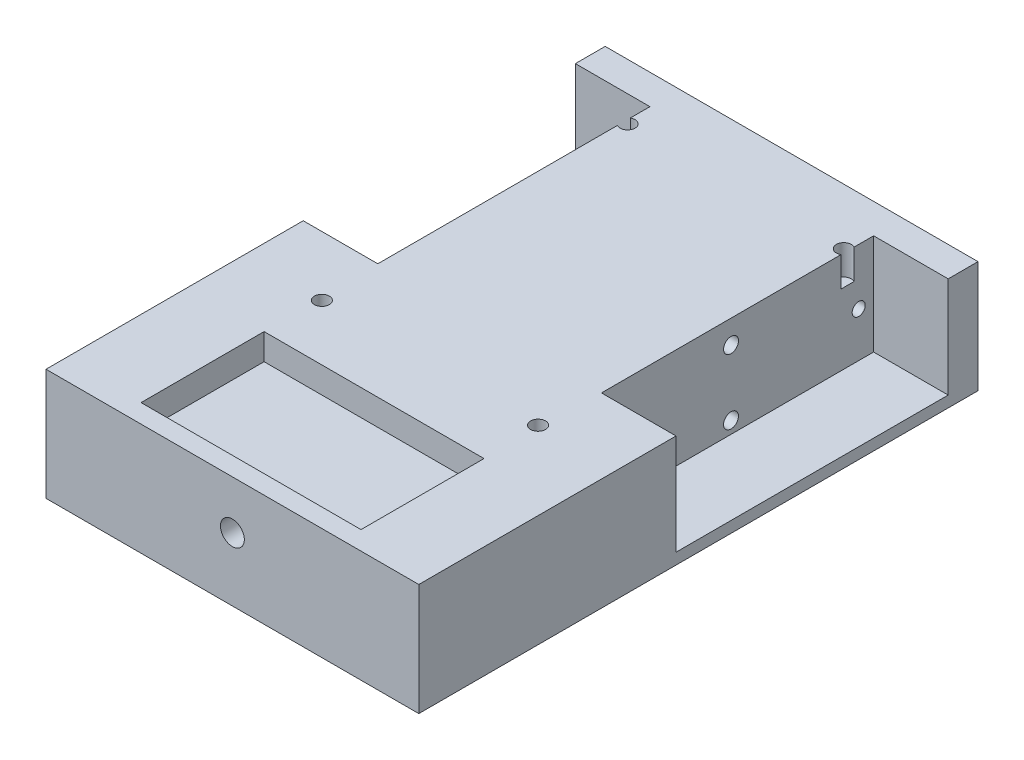
SolidWorks part; units mm, degrees
ref_plane "Front Plane" through (0, 0, 0) normal (0, 0, 1) x (1, 0, 0)
ref_plane "Top Plane" through (0, 0, 0) normal (0, 1, 0) x (1, 0, 0)
ref_plane "Right Plane" through (0, 0, 0) normal (1, 0, 0) x (0, 0, -1)
sketch "Sketch1" plane through (0, 0, 0) normal (0, 1, 0) x (1, 0, 0)
  line L1 (-50, 75) -> (50, 75)
  line L2 (-50, 75) -> (-50, -75)
  line L3 (-50, -75) -> (50, -75)
  line L4 (50, 75) -> (50, -75)
  line L5 (-50, 75) -> (50, -75) construction
  line L6 (-50, -75) -> (50, 75) construction
  point P0 (0, 0)
  dimension "D1" = 100
  dimension "D2" = 150
extrude "box" add sketch "Sketch1" against normal blind 30
sketch "Sketch2" plane through (50, 0, 0) normal (1, 0, 0) x (0, 0, -1)
  line L0 (0, 0) -> (0, -30) construction
  line L1 (-75, -30) -> (75, -30) construction
  line L2 (-75, -15) -> (75, -15) construction
  line L3 (-75, -30) -> (-75, 0) construction
  line L4 (75, -30) -> (75, 0) construction
  line L6 (-6, -3) -> (67, -3)
  line L7 (-6, -3) -> (-6, -27)
  line L8 (-6, -27) -> (67, -27)
  line L9 (67, -3) -> (67, -27)
  line L10 (-6, -3) -> (67, -27) construction
  line L11 (-6, -27) -> (67, -3) construction
  point P11 (30.5, -15)
  dimension "D1" = 24
  dimension "D2" = 73
  dimension "D3" = 8
extrude "motor compartment" cut sketch "Sketch2" against normal blind 20
sketch "Sketch3" plane through (50, 0, 0) normal (1, 0, 0) x (0, 0, -1)
  line L0 (-75, 0) -> (75, 0) construction
  line L1 (-6, -3) -> (4, -3)
  line L2 (-6, -3) -> (-6, 0)
  line L3 (-6, 0) -> (4, 0)
  line L4 (4, -3) -> (4, 0)
  dimension "D1" = 10
extrude "motor wire passthrough" cut sketch "Sketch3" against normal up to surface (20 mm away) up to face at (30, -15, -30.5)
sketch "Sketch4" plane through (30, 0, 0) normal (1, 0, 0) x (0, 0, -1)
  line L0 (67, -15) -> (-49933, -15) construction
  line L1 (67, -27) -> (67, -3) construction
  line L2 (67, -27) -> (67, -3) construction
  line L3 (67, -27) -> (67, -3) construction
  line L4 (28.75, -3) -> (28.75, -27) construction
  line L5 (67, -3) -> (4, -3) construction
  line L6 (-6, -27) -> (67, -27) construction
  circle A0 centre (63, -15) radius 1.75
  circle A1 centre (28.75, -6.25) radius 2
  circle A2 centre (28.75, -23.75) radius 2
  point P4 (67, -15)
  point P19 (0, 0)
  dimension "D1" = 3.5
  dimension "D4" = 4
  dimension "D2" = 4
  dimension "D3" = 34.25
  dimension "D5" = 8.75
extrude "motor screw mount" cut sketch "Sketch4" against normal blind 10
sketch "Sketch9" plane through (50, 0, 0) normal (1, 0, 0) x (0, 0, -1)
  line L1 (4, 0) -> (67, 0)
  line L2 (4, 0) -> (4, -3)
  line L3 (4, -3) -> (67, -3)
  line L4 (67, 0) -> (67, -3)
extrude "remove motor wall" cut sketch "Sketch9" against normal up to surface (20 mm away) up to face at (30, -15, -64.75)
mirror "motor compartment mirror" about plane through (0, 0, 0) normal (1, 0, 0) of "remove motor wall", "motor wire passthrough", "motor compartment", "motor screw mount"
sketch "Sketch5" plane through (0, 0, 0) normal (0, 1, 0) x (1, 0, 0)
  line L0 (0, 75) -> (0, -75) construction
  line L1 (50, 75) -> (-50, 75) construction
  line L2 (-50, -75) -> (50, -75) construction
  line L3 (50, 60) -> (-50, 60) construction
  line L4 (50, 67) -> (50, 75) construction
  line L5 (-50, 75) -> (-50, 67) construction
  line L6 (50, -22) -> (-50, -22) construction
  line L7 (50, -75) -> (50, -6) construction
  line L8 (-50, -6) -> (-50, -75) construction
  circle A0 centre (-29, 60) radius 2
  circle A1 centre (-29, -22) radius 2
  circle A2 centre (29, 60) radius 2
  circle A3 centre (29, -22) radius 2
  dimension "D4" = 4
  dimension "D3" = 4
  dimension "D1" = 15
  dimension "D2" = 82
  dimension "D5" = 29
extrude "Maker Pi mount holes" cut sketch "Sketch5" against normal blind 8
sketch "Sketch8" plane through (0, 0, 0) normal (0, 1, 0) x (1, 0, 0)
  line L0 (0, 0) -> (0, -75) construction
  line L1 (-50, -75) -> (50, -75) construction
  line L3 (-29.5, -70) -> (29.5, -70)
  line L4 (-29.5, -70) -> (-29.5, -37)
  line L5 (-29.5, -37) -> (29.5, -37)
  line L6 (29.5, -70) -> (29.5, -37)
  line L7 (-29.5, -70) -> (29.5, -37) construction
  line L8 (-29.5, -37) -> (29.5, -70) construction
  point P5 (0, -53.5)
  dimension "D1" = 59
  dimension "D2" = 33
  dimension "D3" = 5
extrude "battery bank holder" cut sketch "Sketch8" against normal blind 7
sketch "Sketch6" plane through (0, -30, 0) normal (0, -1, 0) x (1, 0, 0)
  line L0 (0, 0) -> (0, 75) construction
  line L1 (-50, 75) -> (50, 75) construction
  line L2 (-50, 75) -> (50, 75) construction
  line L4 (-12, 65) -> (12, 65)
  line L5 (-12, 65) -> (-12, 37)
  line L6 (-12, 37) -> (12, 37)
  line L7 (12, 65) -> (12, 37)
  line L8 (-12, 65) -> (12, 37) construction
  line L9 (-12, 37) -> (12, 65) construction
  point P5 (0, 51)
  dimension "D1" = 24
  dimension "D2" = 28
  dimension "D3" = 10
extrude "caster mount" cut sketch "Sketch6" against normal blind 1
sketch "Sketch7" plane through (0, 0, 75) normal (0, 0, 1) x (1, 0, 0)
  line L0 (0, 0) -> (0, -30) construction
  line L1 (-50, -30) -> (50, -30) construction
  circle A0 centre (0, -13) radius 3.2
  dimension "D1" = 6.4
  dimension "D2" = 13
extrude "front mount hole" cut sketch "Sketch7" against normal blind 25.4
mirror "back mount hole" about plane through (0, 0, 0) normal (0, 0, 1) of "front mount hole"
equation "\"D5@Sketch4\"=17.5mm/2"
equation "\"D4@Sketch5\"=\"D3@Sketch5\""
equation "\"D5@Sketch5\"=58mm/2"
